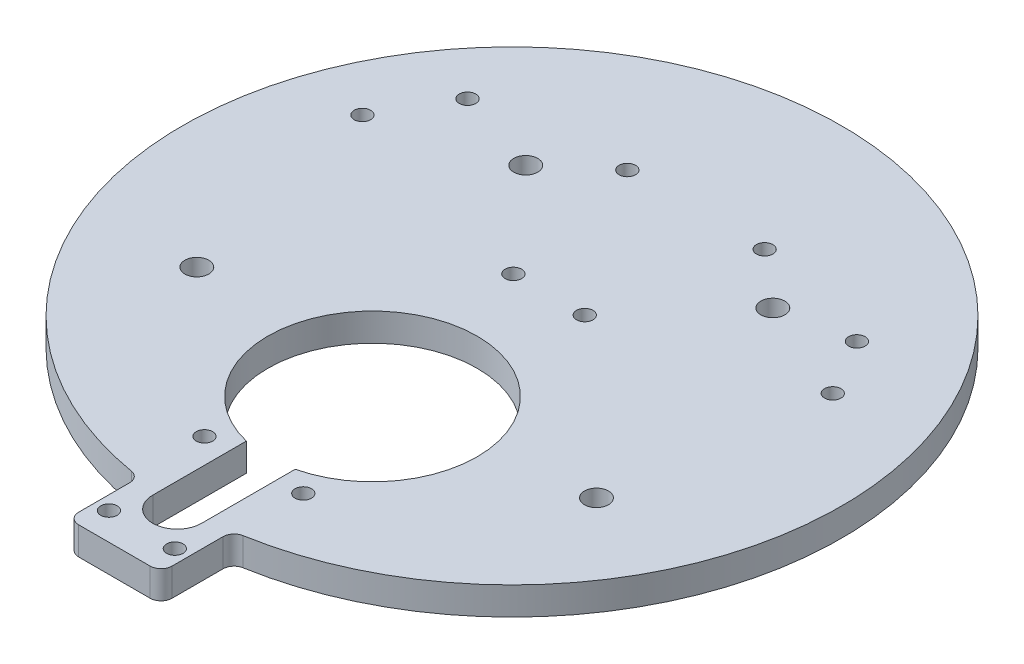
SolidWorks part; units mm, degrees
ref_plane "Front Plane" through (0, 0, 0) normal (0, 0, 1) x (1, 0, 0)
ref_plane "Top Plane" through (0, 0, 0) normal (0, 1, 0) x (1, 0, 0)
ref_plane "Right Plane" through (0, 0, 0) normal (1, 0, 0) x (0, 0, -1)
sketch "Sketch1" plane through (0, 0, 0) normal (0, 1, 0) x (1, 0, 0)
  circle A0 centre (0, 0) radius 60
  dimension "D1" = 120
extrude "Boss-Extrude1" add sketch "Sketch1" along normal blind 5.08
sketch "Sketch2" plane through (0, 5.08, 0) normal (0, 1, 0) x (1, 0, 0)
  line L0 (0, 0) -> (0, 60) construction
  line L1 (-51.9615, -30) -> (0, 0) construction
  line L2 (0, 0) -> (51.9615, -30) construction
  circle A0 centre (0, 0) radius 60 construction
  circle A3 centre (-36.3861, -21.0075) radius 2.1828
  dimension "D3" = 42.015
  dimension "D6" = 4.3656
  dimension "D1" = 120
  dimension "D2" = 120
extrude "Cut-Extrude1" cut sketch "Sketch2" against normal through all
ref_axis "Axis1" through (0, 5.08, 0) along (0, -1, 0)
pattern_circular "CirPattern1" count 2 every 120 about axis through (0, 5.08, 0) along (0, -1, 0) of "Cut-Extrude1" reverse direction yes
sketch "Sketch3" plane through (0, 5.08, 0) normal (0, 1, 0) x (1, 0, 0)
  line L0 (0, 0) -> (0, 60) construction
  line L1 (-6.5, 6.75) -> (6.5, 6.75) construction
  line L2 (0, 0) -> (51.9615, 30) construction
  line L3 (35.4212, 27.3787) -> (41.4212, 16.9863) construction
  line L4 (0, 0) -> (-51.9615, 30) construction
  line L5 (-45.2944, 18.0678) -> (-38.2944, 30.1922) construction
  circle A0 centre (-6.5, 6.75) radius 1.5
  circle A1 centre (6.5, 6.75) radius 1.5
  circle A2 centre (0, 0) radius 60 construction
  circle A3 centre (-12.5, 33.5) radius 1.5
  circle A4 centre (12.5, 33.5) radius 1.5
  circle A5 centre (35.4212, 27.3787) radius 1.5
  circle A6 centre (41.4212, 16.9863) radius 1.5
  circle A7 centre (-45.2944, 18.0678) radius 1.5
  circle A8 centre (-38.2944, 30.1922) radius 1.5
  dimension "D1" = 3
  dimension "D4" = 25
  dimension "D5" = 33.5
  dimension "D10" = 14
  dimension "D11" = 48.26
  dimension "D2" = 13
  dimension "D3" = 6.75
  dimension "D6" = 44.365
  dimension "D7" = 60
  dimension "D8" = 12
  dimension "D9" = 60
extrude "Cut-Extrude2" cut sketch "Sketch3" against normal through all
sketch "Sketch5" plane through (0, 5.08, 0) normal (0, 1, 0) x (1, 0, 0)
  line L0 (0, 60) -> (0, 0) construction
  circle A0 centre (-22.5, 25) radius 2.1828
  circle A1 centre (22.5, 25) radius 2.1828
  circle A2 centre (0, 0) radius 60 construction
  circle A3 centre (-36.3861, -21.0075) radius 2.1828 construction
  dimension "D1" = 45
  dimension "D2" = 25
extrude "Cut-Extrude4" cut sketch "Sketch5" against normal through all
sketch "Sketch6" plane through (0, 5.08, 0) normal (0, 1, 0) x (1, 0, 0)
  circle A0 centre (0, -25.4) radius 19.05
  dimension "D1" = 38.1
  dimension "D2" = 25.4
extrude "Cut-Extrude5" cut sketch "Sketch6" against normal through all
sketch "Sketch9" plane through (0, 5.08, 0) normal (0, 1, 0) x (1, 0, 0)
  line L1 (-8.5, -72.3949) -> (8.5, -72.3949)
  line L2 (-8.5, -72.3949) -> (-8.5, -59.3949)
  line L3 (-8.5, -59.3949) -> (8.5, -59.3949)
  line L4 (8.5, -72.3949) -> (8.5, -59.3949)
  line L5 (-8.5, -72.3949) -> (8.5, -59.3949) construction
  line L6 (-8.5, -59.3949) -> (8.5, -72.3949) construction
  circle A0 centre (0, 0) radius 60 construction
  point P0 (0, -65.8949)
  dimension "D1" = 17
  dimension "D2" = 13
extrude "Boss-Extrude2" add sketch "Sketch9" against normal up to surface (5.08 mm away) up to face at (0, 0, 44.45)
sketch "Sketch7" plane through (0, 5.08, 0) normal (0, 1, 0) x (1, 0, 0)
  line L0 (0, -43.9242) -> (0, -60.9649) construction
  line L1 (-8.5, -72.3949) -> (8.5, -72.3949) construction
  line L2 (-4.445, -60.9649) -> (-4.445, -43.9242)
  line L3 (-4.445, -43.9242) -> (4.445, -43.9242)
  line L4 (4.445, -60.9649) -> (4.445, -43.9242)
  line L5 (-4.445, -60.9649) -> (4.445, -43.9242) construction
  line L6 (-4.445, -43.9242) -> (4.445, -60.9649) construction
  circle A0 centre (0, -25.4) radius 19.05 construction
  circle A1 centre (-9, -47) radius 1.5
  arc A2 (-4.445, -60.9649) -> (4.445, -60.9649) centre (0, -60.9649) ccw
  circle A3 centre (-6, -67.3949) radius 1.5
  circle A4 centre (6, -67.3949) radius 1.5
  circle A5 centre (9, -47) radius 1.5
  point P0 (0, -52.4445)
  dimension "D3" = 3
  dimension "D4" = 12
  dimension "D5" = 5
  dimension "D6" = 47
  dimension "D7" = 18
  dimension "D1" = 8.89
  dimension "D2" = 11.43
extrude "Cut-Extrude6" cut sketch "Sketch7" against normal through all
fillet "Fillet1" radius 2 2 edges at (8.5, 2.54, 72.3949) (-8.5, 2.54, 72.3949)
fillet "Fillet2" radius 2 2 edges at (8.5, 2.54, 59.3949) (-8.5, 2.54, 59.3949)
